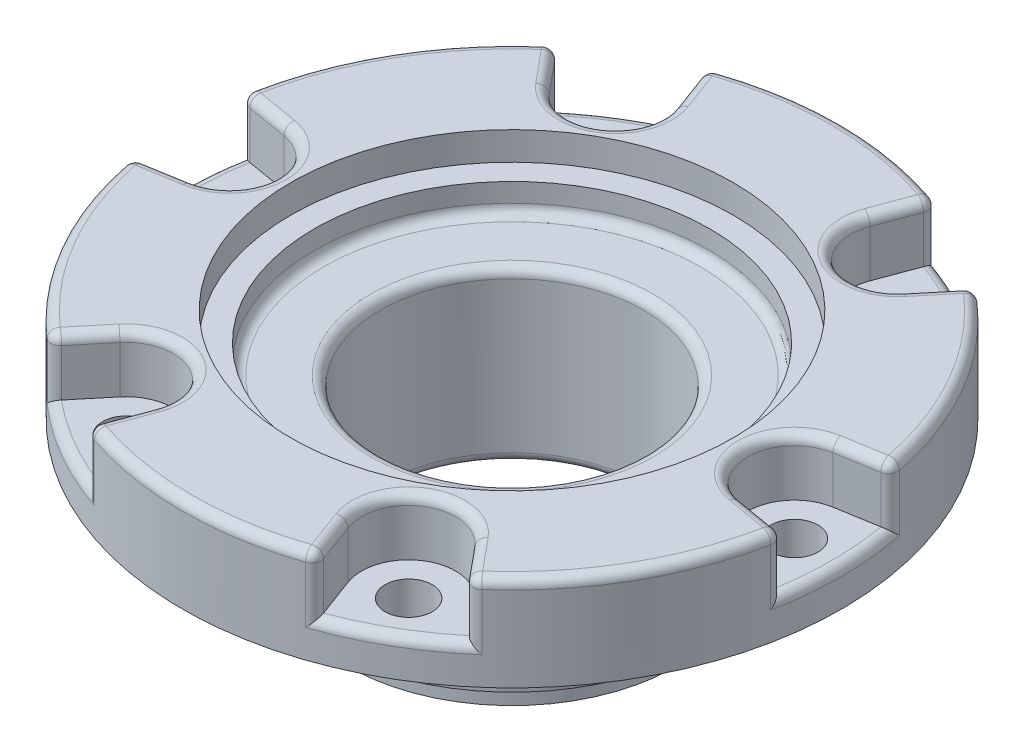
SolidWorks part; units mm, degrees
material "ABS"
ref_plane "Front Plane" through (0, 0, 0) normal (0, 0, 1) x (1, 0, 0)
ref_plane "Top Plane" through (0, 0, 0) normal (0, 1, 0) x (1, 0, 0)
ref_plane "Right Plane" through (0, 0, 0) normal (1, 0, 0) x (0, 0, -1)
sketch "Sketch1" plane through (0, 0, 0) normal (0, 0, 1) x (1, 0, 0)
  line L0 (-64.62, -11.0938) -> (-64.62, 12.9062) construction
  line L1 (-47.12, -8.0938) -> (-47.12, -11.0938)
  line L2 (-29.62, 2.9062) -> (-44.62, 2.9062)
  line L3 (-29.62, 6.9062) -> (-29.62, 2.9062)
  line L5 (-44.62, -8.0938) -> (-44.62, 2.9062)
  line L6 (-47.12, -8.0938) -> (-44.62, -8.0938)
  line L7 (-47.12, -11.0938) -> (-50.62, -11.0938)
  line L8 (-39.62, 12.9062) -> (-29.62, 12.9062)
  line L9 (-29.62, 12.9062) -> (-29.62, 6.9062)
  line L11 (-39.62, 12.9062) -> (-41.12, 12.9062)
  line L13 (-43.62, 9.9062) -> (-41.12, 9.9062)
  line L14 (-41.12, 9.9062) -> (-41.12, 12.9062)
  line L16 (-43.62, 6.9062) -> (-50.62, 6.9062)
  line L17 (-43.62, 9.9062) -> (-43.62, 6.9062)
  line L18 (-50.62, -11.0938) -> (-50.62, 6.9062)
revolve "Revolve1" add sketch "Sketch1" angle 360 about L0
sketch "Sketch2" plane through (0, 12.9062, 0) normal (0, 1, 0) x (1, 0, 0)
  line L0 (-93.7867, -4.9301) -> (-99.1305, -5.8333)
  line L1 (-93.7867, 4.9301) -> (-99.1305, 5.8333)
  line L2 (-74.9338, -27.7241) -> (-76.8235, -32.8036)
  line L3 (-83.4729, -22.794) -> (-86.9271, -26.9703)
  line L4 (-45.7671, -22.794) -> (-42.313, -26.9703)
  line L5 (-54.3063, -27.7241) -> (-52.4166, -32.8036)
  line L6 (-35.4534, 4.9301) -> (-30.1096, 5.8333)
  line L7 (-35.4534, -4.9301) -> (-30.1096, -5.8333)
  line L8 (-54.3063, 27.7241) -> (-52.4166, 32.8036)
  line L9 (-45.7671, 22.794) -> (-42.313, 26.9703)
  line L10 (-83.4729, 22.794) -> (-86.9271, 26.9703)
  line L11 (-74.9338, 27.7241) -> (-76.8235, 32.8036)
  line L12 (-64.62, 35) -> (-64.62, -35) construction
  arc A0 (-99.1305, 5.8333) -> (-99.1305, -5.8333) centre (-64.62, 0) ccw
  arc A1 (-93.7867, -4.9301) -> (-93.7867, 4.9301) centre (-94.62, 0) ccw
  arc A2 (-74.9338, -27.7241) -> (-83.4729, -22.794) centre (-79.62, -25.9808) ccw
  arc A3 (-45.7671, -22.794) -> (-54.3063, -27.7241) centre (-49.62, -25.9808) ccw
  arc A4 (-35.4534, 4.9301) -> (-35.4534, -4.9301) centre (-34.62, 0) ccw
  arc A5 (-54.3063, 27.7241) -> (-45.7671, 22.794) centre (-49.62, 25.9808) ccw
  arc A6 (-83.4729, 22.794) -> (-74.9338, 27.7241) centre (-79.62, 25.9808) ccw
  circle A7 centre (-64.62, 0) radius 35 construction
  arc A8 (-86.9271, -26.9703) -> (-76.8235, -32.8036) centre (-64.62, 0) ccw
  arc A9 (-52.4166, -32.8036) -> (-42.313, -26.9703) centre (-64.62, 0) ccw
  arc A10 (-30.1096, -5.8333) -> (-30.1096, 5.8333) centre (-64.62, 0) ccw
  arc A11 (-42.313, 26.9703) -> (-52.4166, 32.8036) centre (-64.62, 0) ccw
  arc A12 (-76.8235, 32.8036) -> (-86.9271, 26.9703) centre (-64.62, 0) ccw
extrude "Cut-Extrude1" cut sketch "Sketch2" against normal blind 6
sketch "Sketch3" plane through (0, 12.9062, 0) normal (0, 1, 0) x (1, 0, 0)
  line L0 (-64.62, 35) -> (-64.62, -35) construction
  circle A1 centre (-94.62, 0) radius 2.5
  circle A2 centre (-79.62, -25.9808) radius 2.5
  circle A3 centre (-49.62, -25.9808) radius 2.5
  circle A4 centre (-34.62, 0) radius 2.5
  circle A5 centre (-49.62, 25.9808) radius 2.5
  circle A6 centre (-79.62, 25.9808) radius 2.5
  arc A7 (-52.4166, 32.8036) -> (-76.8235, 32.8036) centre (-64.62, 0) ccw construction
  arc A8 (-76.8235, -32.8036) -> (-52.4166, -32.8036) centre (-64.62, 0) ccw construction
extrude "Cut-Extrude2" cut sketch "Sketch3" against normal through all
fillet "Zaokrąglenie1" radius 1 45 edges at (-64.62, 6.9062, -14) (-64.62, 12.9062, 35) (-64.62, 6.9062, -21) (-75.8786, 12.9062, 30.2639) (-77.12, 12.9062, 21.6506) (-96.4586, 12.9062, 5.3817) (-89.62, 12.9062, 0) (-85.2, 12.9062, -24.8822) (-77.12, 12.9062, -21.6506) (-53.3615, 12.9062, -30.2639) (-52.12, 12.9062, -21.6506) (-32.7815, 12.9062, -5.3817) (-32.7815, 12.9062, 5.3817) (-44.0401, 12.9062, 24.8822) (-52.12, 12.9062, 21.6506) (-94.9309, 12.9062, 17.5) (-86.9271, 9.9062, 26.9703) (-82.12, 6.9062, 30.3109) (-76.8235, 9.9062, 32.8036) (-52.4166, 9.9062, 32.8036) (-47.12, 6.9062, 30.3109) (-42.313, 9.9062, 26.9703) (-34.3092, 12.9062, 17.5) (-30.1096, 9.9062, 5.8333) (-29.62, 6.9062, 0) (-30.1096, 9.9062, -5.8333) (-34.3092, 12.9062, -17.5) (-42.313, 9.9062, -26.9703) (-47.12, 6.9062, -30.3109) (-52.4166, 9.9062, -32.8036) (-64.62, 12.9062, -35) (-76.8235, 9.9062, -32.8036) (-82.12, 6.9062, -30.3109) (-86.9271, 9.9062, -26.9703) (-94.9309, 12.9062, -17.5) (-99.1305, 9.9062, -5.8333) (-99.62, 6.9062, 0) (-99.1305, 9.9062, 5.8333) (-85.2, 12.9062, 24.8822) (-96.4586, 12.9062, -5.3817) (-75.8786, 12.9062, -30.2639) (-44.0401, 12.9062, -24.8822) (-39.62, 12.9062, 0) (-53.3615, 12.9062, 30.2639) (-64.62, -11.0938, -14)
